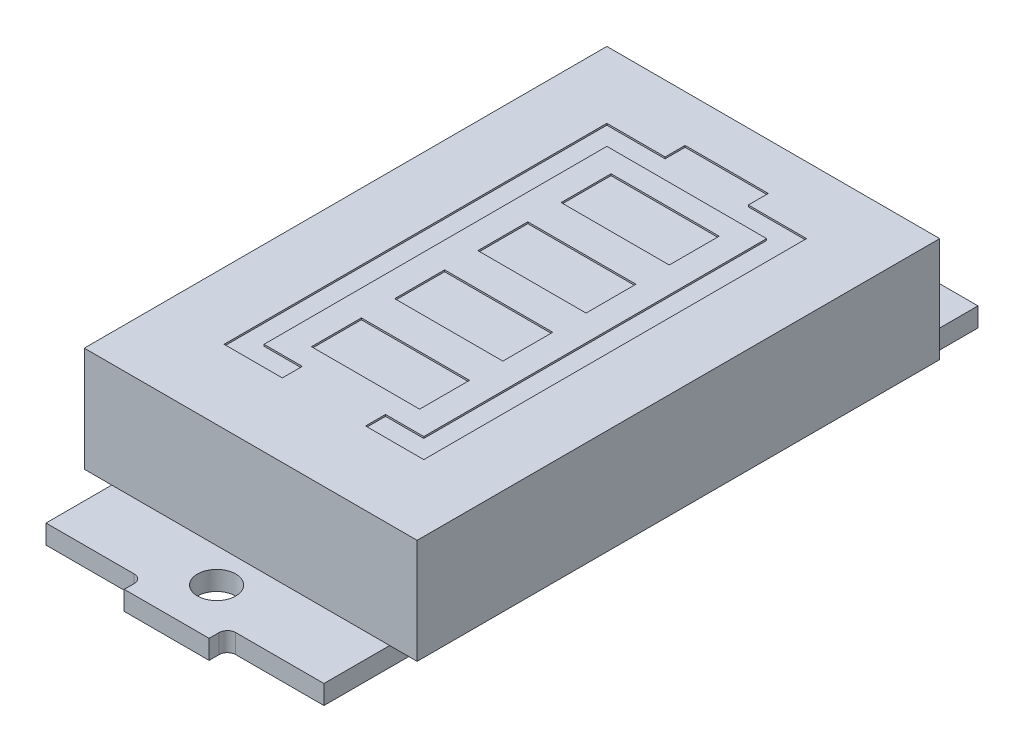
SolidWorks part; units mm, degrees
ref_plane "Plan de face" through (0, 0, 0) normal (0, 0, 1) x (1, 0, 0)
ref_plane "Plan de dessus" through (0, 0, 0) normal (0, 1, 0) x (1, 0, 0)
ref_plane "Plan de droite" through (0, 0, 0) normal (1, 0, 0) x (0, 0, -1)
sketch "Esquisse1" plane through (0, 0, 0) normal (0, 1, 0) x (1, 0, 0)
  line L0 (0, 0) -> (-8.35, 0) construction
  line L1 (0, -20.75) -> (0, 20.75) construction
  line L2 (-8.35, -19.65) -> (-8.35, 19.65)
  line L3 (-8.35, 19.65) -> (-2.55, 19.65)
  line L4 (-2.55, 19.65) -> (-2.55, 20.75)
  line L5 (-2.55, 20.75) -> (2.55, 20.75)
  line L6 (2.55, 19.65) -> (2.55, 20.75)
  line L7 (8.35, 19.65) -> (2.55, 19.65)
  line L8 (8.35, -19.65) -> (8.35, 19.65)
  line L9 (-8.35, -19.65) -> (-8.35, 19.65)
  line L10 (-8.35, 19.65) -> (-2.55, 19.65)
  line L11 (-2.55, 19.65) -> (-2.55, 20.75)
  line L12 (2.55, 19.65) -> (2.55, 20.75)
  line L13 (8.35, 19.65) -> (2.55, 19.65)
  line L14 (8.35, -19.65) -> (8.35, 19.65)
  line L15 (8.35, -19.65) -> (2.55, -19.65)
  line L16 (2.55, -19.65) -> (2.55, -20.75)
  line L17 (-2.55, -19.65) -> (-2.55, -20.75)
  line L18 (-8.35, -19.65) -> (-2.55, -19.65)
  line L19 (8.35, -19.65) -> (2.55, -19.65)
  line L20 (2.55, -19.65) -> (2.55, -20.75)
  line L21 (-2.55, -20.75) -> (2.55, -20.75)
  line L22 (-2.55, -19.65) -> (-2.55, -20.75)
  line L23 (-8.35, -19.65) -> (-2.55, -19.65)
  circle A0 centre (0, 17.75) radius 1.15
  circle A1 centre (0, -17.75) radius 1.15
  point P20 (8.35, 0)
  dimension "D6" = 2.3
  dimension "D8" = 2.3
  dimension "D1" = 20.75
  dimension "D2" = 1.1
  dimension "D3" = 2.55
  dimension "D4" = 8.35
  dimension "D5" = 3
  dimension "D7" = 3
extrude "Boss.-Extru.1" add sketch "Esquisse1" along normal blind 1.15 contours L17 L21 L16 L15 L8 L7 L6 L5 L4 L3 L2 L18 A1 A0 region at (0, 0, 0)
fillet "Congé1" radius 0.5 4 edges at (-2.55, 0.575, -19.65) (2.55, 0.575, -19.65) (-2.55, 0.575, 19.65) (2.55, 0.575, 19.65)
sketch "Esquisse2" plane through (0, 1.15, 0) normal (0, 1, 0) x (1, 0, 0)
  line L1 (-10, -15.7) -> (10, -15.7)
  line L2 (-10, -15.7) -> (-10, 15.7)
  line L3 (-10, 15.7) -> (10, 15.7)
  line L4 (10, -15.7) -> (10, 15.7)
  line L5 (-10, -15.7) -> (10, 15.7) construction
  line L6 (-10, 15.7) -> (10, -15.7) construction
  point P0 (0, 0)
  dimension "D1" = 31.4
  dimension "D2" = 20
extrude "Boss.-Extru.2" add sketch "Esquisse2" along normal blind 6.3
sketch "Esquisse4" plane through (0, 7.45, 0) normal (0, 1, 0) x (1, 0, 0)
  line L0 (0, 15.7) -> (0, -15.7) construction
  line L1 (10, 15.7) -> (-10, 15.7) construction
  line L2 (-10, -15.7) -> (10, -15.7) construction
  line L3 (-2.5, -10.1) -> (-2.5, -11.3)
  line L4 (-2.5, -11.3) -> (-6, -11.3)
  line L5 (-6, -11.3) -> (-6, 11.7)
  line L6 (-6, 11.7) -> (-2.5, 11.7)
  line L7 (-2.5, 11.7) -> (-2.5, 12.9)
  line L8 (-2.5, 12.9) -> (2.5, 12.9)
  line L9 (0, 12.9) -> (0, 10.5)
  line L10 (4.8, 10.5) -> (-4.8, 10.5)
  line L11 (-4.8, 10.5) -> (-4.8, -10.1)
  line L12 (-4.8, -10.1) -> (-2.5, -10.1)
  line L13 (3.25, 9.2) -> (-3.25, 9.2)
  line L14 (-3.25, 9.2) -> (-3.25, 6.2)
  line L15 (-3.25, 6.2) -> (3.25, 6.2)
  line L16 (0, 6.2) -> (0, 4.2)
  line L17 (3.25, 4.2) -> (-3.25, 4.2)
  line L18 (-3.25, 4.2) -> (-3.25, 1.2)
  line L19 (-3.25, 1.2) -> (3.25, 1.2)
  line L20 (3.25, -0.8) -> (-3.25, -0.8)
  line L21 (-3.25, -0.8) -> (-3.25, -3.8)
  line L22 (-3.25, -3.8) -> (3.25, -3.8)
  line L23 (3.25, -5.8) -> (-3.25, -5.8)
  line L24 (-3.25, -5.8) -> (-3.25, -8.8)
  line L25 (-3.25, -8.8) -> (3.25, -8.8)
  line L26 (-3.25, -7.3) -> (3.25, -7.3) construction
  line L27 (-3.25, -2.3) -> (3.25, -2.3) construction
  line L28 (-3.25, 2.7) -> (3.25, 2.7) construction
  line L29 (-3.25, 7.7) -> (3.25, 7.7) construction
  line L30 (3.25, -5.8) -> (3.25, -8.8)
  line L31 (3.25, -0.8) -> (3.25, -3.8)
  line L32 (3.25, 4.2) -> (3.25, 1.2)
  line L33 (3.25, 9.2) -> (3.25, 6.2)
  line L34 (4.8, -10.1) -> (2.5, -10.1)
  line L35 (4.8, 10.5) -> (4.8, -10.1)
  line L36 (2.5, 11.7) -> (2.5, 12.9)
  line L37 (6, 11.7) -> (2.5, 11.7)
  line L38 (6, -11.3) -> (6, 11.7)
  line L39 (2.5, -11.3) -> (6, -11.3)
  line L40 (2.5, -10.1) -> (2.5, -11.3)
  point P42 (0, 7.7)
  point P43 (0, 2.7)
  point P44 (0, -2.3)
  point P45 (0, -7.3)
  point P46 (0, -8.8)
  point P47 (0, -5.8)
  point P48 (0, -3.8)
  point P49 (0, -0.8)
  point P50 (0, 1.2)
  point P53 (0, 9.2)
  dimension "D1" = 23
  dimension "D2" = 1.2
  dimension "D3" = 1.2
  dimension "D4" = 1.2
  dimension "D5" = 3.5
  dimension "D6" = 6
  dimension "D7" = 1.2
  dimension "D8" = 2.5
  dimension "D9" = 3
  dimension "D10" = 3
  dimension "D11" = 3
  dimension "D12" = 3
  dimension "D13" = 5
  dimension "D14" = 5
  dimension "D15" = 5
  dimension "D16" = 2.8
  dimension "D17" = 13
  dimension "D18" = 3.25
extrude "Enlèv. mat.-Extru.1" cut sketch "Esquisse4" against normal blind 0.1 contours L34 L40 L39 L38 L37 L36 L8 L9 L10 L35 | L12 L11 L10 L9 L8 L7 L6 L5 L4 L3 | L33 L13 L14 L15 | L31 L20 L21 L22 | L30 L23 L24 L25 | L17 L18 L19 L32 region at (-2.7493, 7.45, 10.7) region at (0.2493, 7.45, -11.7) region at (0, 7.45, -7.7) region at (0, 7.45, 2.3) region at (0, 7.45, 7.3)
